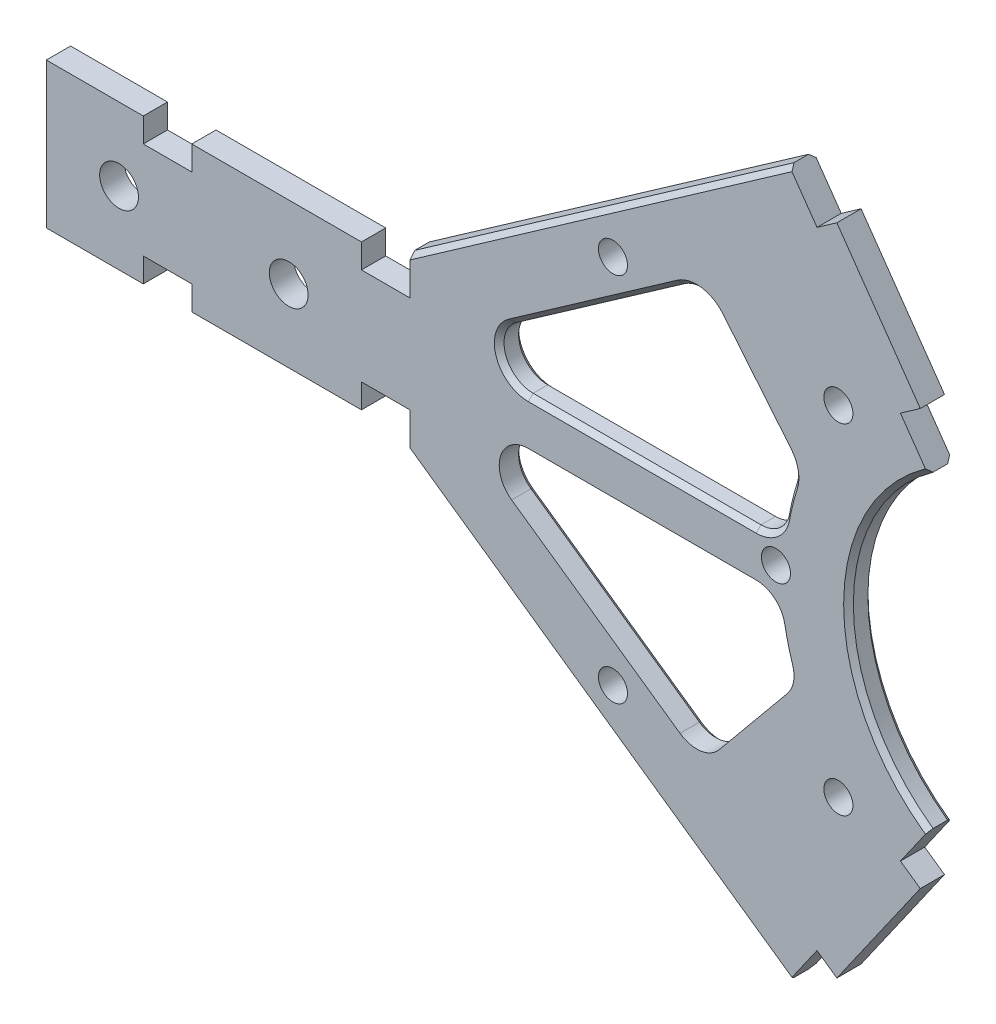
SolidWorks part; units mm, degrees
material "6061-T4 (SS)"
ref_plane "Front Plane" through (0, 0, 0) normal (0, 0, 1) x (1, 0, 0)
ref_plane "Top Plane" through (0, 0, 0) normal (0, 1, 0) x (1, 0, 0)
ref_plane "Right Plane" through (0, 0, 0) normal (1, 0, 0) x (0, 0, -1)
sketch "Sketch1" plane through (0, 0, 0) normal (0, 0, 1) x (1, 0, 0)
  line L0 (90.0339, 0) -> (-472.3272, 0) construction
  line L1 (-204.5, 15) -> (-204.5, -15)
  line L2 (-204.5, 15) -> (-184.5, 15)
  line L3 (-184.5, 15) -> (-184.5, 10)
  line L4 (-184.5, 10) -> (-174.5, 10)
  line L5 (-174.5, 10) -> (-174.5, 15)
  line L6 (-174.5, 15) -> (-139.5, 15)
  line L7 (-139.5, 15) -> (-139.5, 10)
  line L8 (-139.5, 10) -> (-129.5, 10)
  line L9 (-129.5, 10) -> (-129.5, 18)
  line L10 (-129.5, -10) -> (-129.5, -18)
  line L11 (-139.5, -15) -> (-139.5, -10)
  line L12 (-139.5, -10) -> (-129.5, -10)
  line L13 (-174.5, -10) -> (-174.5, -15)
  line L14 (-174.5, -15) -> (-139.5, -15)
  line L15 (-184.5, -15) -> (-184.5, -10)
  line L16 (-184.5, -10) -> (-174.5, -10)
  line L17 (-204.5, -15) -> (-184.5, -15)
  line L18 (-129.5, 18) -> (-51.271, 72.7765)
  line L19 (-129.5, -18) -> (-51.271, -72.7765)
  line L20 (-51.271, 72.7765) -> (-45.5352, 64.585)
  line L21 (-45.5352, 64.585) -> (-41.4395, 67.4529)
  line L22 (-41.4395, 67.4529) -> (-24.2322, 42.8784)
  line L23 (-24.2322, 42.8784) -> (-28.3279, 40.0105)
  line L24 (-28.3279, 40.0105) -> (-22.5922, 31.8189)
  line L25 (-28.3279, -40.0105) -> (-22.5922, -31.8189)
  line L26 (-24.2322, -42.8784) -> (-28.3279, -40.0105)
  line L27 (-41.4395, -67.4529) -> (-24.2322, -42.8784)
  line L28 (-45.5352, -64.585) -> (-41.4395, -67.4529)
  line L29 (-51.271, -72.7765) -> (-45.5352, -64.585)
  line L30 (-105.0851, 4.68) -> (-58.0851, 4.68)
  line L32 (-51.6443, 21.7379) -> (-65.7228, 38.8165)
  line L33 (-73.794, 39.9149) -> (-108.5266, 15.5949)
  line L34 (-105.0851, -4.68) -> (-58.0851, -4.68)
  line L36 (-51.6443, -21.7379) -> (-65.7228, -38.8165)
  line L37 (-73.794, -39.9149) -> (-108.5266, -15.5949)
  circle A0 centre (0, 0) radius 54 construction
  circle A1 centre (-54, 0) radius 3
  circle A2 centre (-41.1218, 35) radius 3
  circle A3 centre (-41.1218, -35) radius 3
  circle A4 centre (-154.5, 0) radius 4
  circle A5 centre (-189.5, 0) radius 4
  arc A6 (-22.5922, 31.8189) -> (-22.5922, -31.8189) centre (-0.041, 0) ccw
  circle A7 centre (-87.6218, -38.25) radius 3
  circle A8 centre (-87.6218, 38.25) radius 3
  arc A9 (-58.0851, 4.68) -> (-52.184, 9.595) centre (-58.0851, 10.68) ccw
  arc A10 (-50.5569, 16.1007) -> (-51.6443, 21.7379) centre (-56.274, 17.9214) ccw
  arc A12 (-108.5266, 15.5949) -> (-105.0851, 4.68) centre (-105.0851, 10.68) ccw
  arc A13 (-65.7228, 38.8165) -> (-73.794, 39.9149) centre (-70.3525, 35) ccw
  arc A14 (-58.0851, -4.68) -> (-52.184, -9.595) centre (-58.0851, -10.68) cw
  arc A15 (-50.5569, -16.1007) -> (-51.6443, -21.7379) centre (-56.274, -17.9214) cw
  arc A16 (-65.7228, -38.8165) -> (-73.794, -39.9149) centre (-70.3525, -35) cw
  arc A17 (-108.5266, -15.5949) -> (-105.0851, -4.68) centre (-105.0851, -10.68) cw
  arc A18 (-52.184, 9.595) -> (-50.5569, 16.1007) centre (0, 0) cw
  arc A19 (-52.184, -9.595) -> (-50.5569, -16.1007) centre (0, 0) ccw
  dimension "D1" = 108
  dimension "D2" = 6
  dimension "D5" = 70
  dimension "D6" = 8
  dimension "D20" = 39
  dimension "D21" = 46.5
  dimension "D23" = 76.5
  dimension "D24" = 47
  dimension "D25" = 6
  dimension "D3" = 35
  dimension "D4" = 70
  dimension "D7" = 35
  dimension "D8" = 30
  dimension "D9" = 20
  dimension "D10" = 10
  dimension "D11" = 35
  dimension "D12" = 95.5
  dimension "D13" = 36
  dimension "D14" = 5
  dimension "D15" = 15
  dimension "D16" = 204.5
  dimension "D17" = 10
  dimension "D18" = 30
  dimension "D19" = 5
  dimension "D22" = 3.25
  dimension "D26" = 14
  dimension "D27" = 101
  dimension "D28" = 70
  dimension "D29" = 4.68
extrude "Boss-Extrude1" add sketch "Sketch1" along normal blind 5 contours A6 L24 L23 L22 L21 L20 L18 L9 L8 L7 L6 L5 L4 L3 L2 L1 L17 L15 L16 L13 L14 L11 L12 L10 L19 L29 L28 L27 L26 L25 A18 A9 L30 A12 L33 A13 L32 A10 A8 A7 A5 A4 A3 A2 region at (-91.4891, 0, 0)
chamfer "Chamfer1" distance 1 angle 45 30 edges at (-90.3855, -45.3883, 5) (-90.3855, -45.3883, 0) (-39.041, 0, 5) (-39.041, 0, 0) (-90.3855, 45.3883, 5) (-90.3855, 45.3883, 0) (-58.6835, -30.2772, 0) (-50.3826, -19.0578, 0) (-69.5434, -40.9452, 0) (-51.4734, -12.8736, 0) (-91.1603, -27.7549, 0) (-54.2452, -6.0697, 0) (-110.8074, -8.8758, 0) (-81.5851, -4.68, 0) (-50.3826, 19.0578, 5) (-58.6835, 30.2772, 5) (-51.4734, 12.8736, 5) (-69.5434, 40.9452, 5) (-54.2452, 6.0697, 5) (-91.1603, 27.7549, 5) (-81.5851, 4.68, 5) (-110.8074, 8.8758, 5) (-51.4734, 12.8736, 0) (-50.3826, 19.0578, 0) (-54.2452, 6.0697, 0) (-58.6835, 30.2772, 0) (-81.5851, 4.68, 0) (-69.5434, 40.9452, 0) (-110.8074, 8.8758, 0) (-91.1603, 27.7549, 0)
